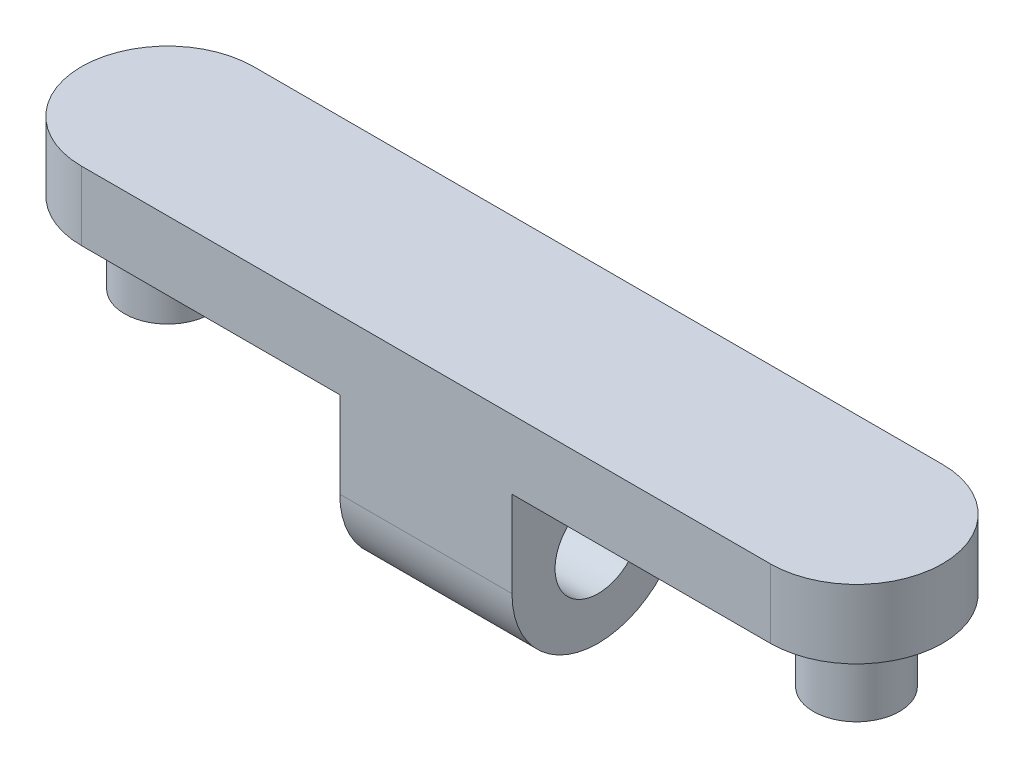
SolidWorks part; units mm, degrees
ref_plane "Front Plane" through (0, 0, 0) normal (0, 0, 1) x (1, 0, 0)
ref_plane "Top Plane" through (0, 0, 0) normal (0, 1, 0) x (1, 0, 0)
ref_plane "Right Plane" through (0, 0, 0) normal (1, 0, 0) x (0, 0, -1)
sketch "Sketch1" plane through (0, 0, 0) normal (0, 1, 0) x (1, 0, 0)
  line L0 (-12.7, 0) -> (12.7, 0) construction
  line L1 (-12.7, 0) -> (12.7, 0) construction
  line L2 (-12.7, 3.175) -> (12.7, 3.175)
  line L3 (-12.7, -3.175) -> (12.7, -3.175)
  circle A0 centre (-12.7, 0) radius 1.5875
  circle A1 centre (12.7, 0) radius 1.5875
  arc A2 (-12.7, 3.175) -> (-12.7, -3.175) centre (-12.7, 0) ccw
  arc A3 (12.7, -3.175) -> (12.7, 3.175) centre (12.7, 0) ccw
  point P3 (0, 0)
  point P6 (0, 0)
  dimension "D2" = 3.175
  dimension "D3" = 3.175
  dimension "D1" = 25.4
extrude "Boss-Extrude1" add sketch "Sketch1" along normal blind 2.54 contours L3 A3 L2 A2
extrude "Boss-Extrude3" add sketch "Sketch1<4>" against normal blind 2.9718 contours A0 | A1
sketch "Sketch1<4>" plane through (0, 0, 0) normal (0, 1, 0) x (1, 0, 0) same geometry as "Sketch1"
sketch "Sketch4" plane through (0, 0, 0) normal (0, -1, 0) x (1, 0, 0)
  line L0 (-12.7, 3.175) -> (12.7, 3.175) construction
  line L1 (-3.175, -3.175) -> (3.175, -3.175)
  line L2 (-3.175, -3.175) -> (-3.175, 3.175)
  line L3 (-3.175, 3.175) -> (3.175, 3.175)
  line L4 (3.175, -3.175) -> (3.175, 3.175)
  line L5 (-3.175, -3.175) -> (3.175, 3.175) construction
  line L6 (-3.175, 3.175) -> (3.175, -3.175) construction
  point P0 (0, 0)
  dimension "D1" = 6.35
extrude "Boss-Extrude4" add sketch "Sketch4" along normal blind 6.35
sketch "Sketch5" plane through (3.175, 0, 0) normal (1, 0, 0) x (0, 0, -1)
  line L0 (-3.175, 0) -> (3.175, -6.35) construction
  line L1 (-3.175, -6.35) -> (-3.175, 0) construction
  line L2 (3.175, 0) -> (-3.175, 0) construction
  circle A0 centre (0, -3.175) radius 1.5875
  dimension "D1" = 3.175
extrude "Cut-Extrude1" cut sketch "Sketch5" against normal blind 6.35
fillet "Fillet1" radius 3.175 2 edges at (0, -6.35, 3.175) (0, -6.35, -3.175)
